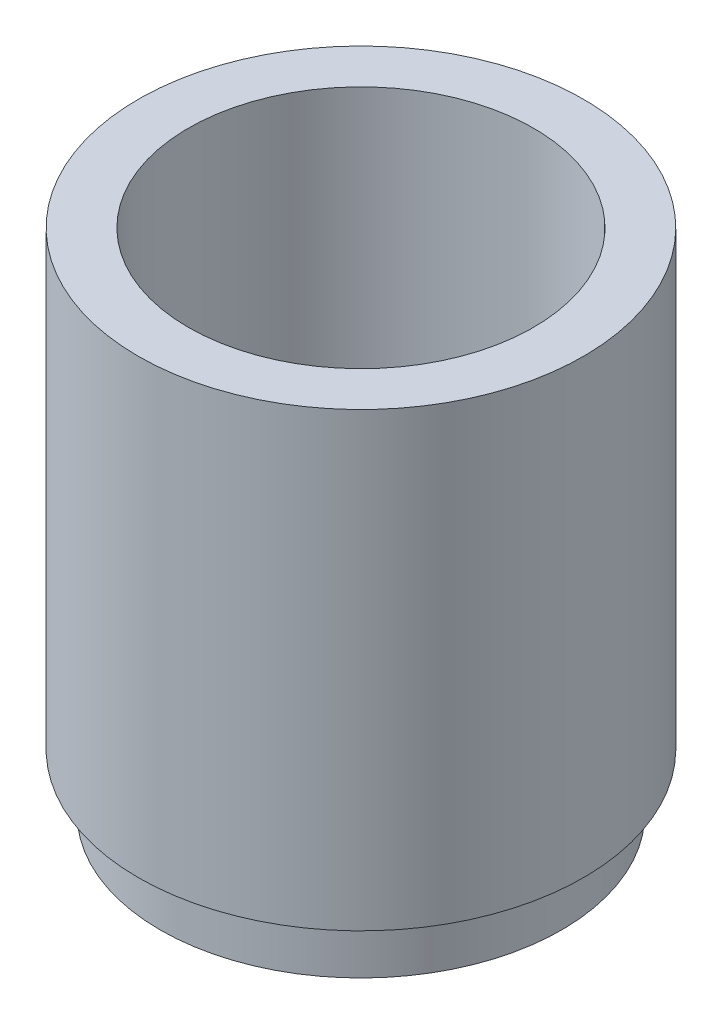
SolidWorks part; units mm, degrees
ref_plane "Front Plane" through (0, 0, 0) normal (0, 0, 1) x (1, 0, 0)
ref_plane "Top Plane" through (0, 0, 0) normal (0, 1, 0) x (1, 0, 0)
ref_plane "Right Plane" through (0, 0, 0) normal (1, 0, 0) x (0, 0, -1)
sketch "Sketch1" plane through (0, 0, 0) normal (0, 1, 0) x (1, 0, 0)
  circle A0 centre (0, 0) radius 8.025
  circle A1 centre (0, 0) radius 6.4
  dimension "D1" = 16.05
  dimension "D2" = 12.8
extrude "Boss-Extrude1" add sketch "Sketch1" along normal blind 2.25
sketch "Sketch2" plane through (0, 2.25, 0) normal (0, 1, 0) x (1, 0, 0)
  circle A0 centre (0, 0) radius 8.9
  circle A1 centre (0, 0) radius 6.9
  dimension "D1" = 17.8
  dimension "D2" = 13.8
extrude "Boss-Extrude2" add sketch "Sketch2" along normal blind 18.05
